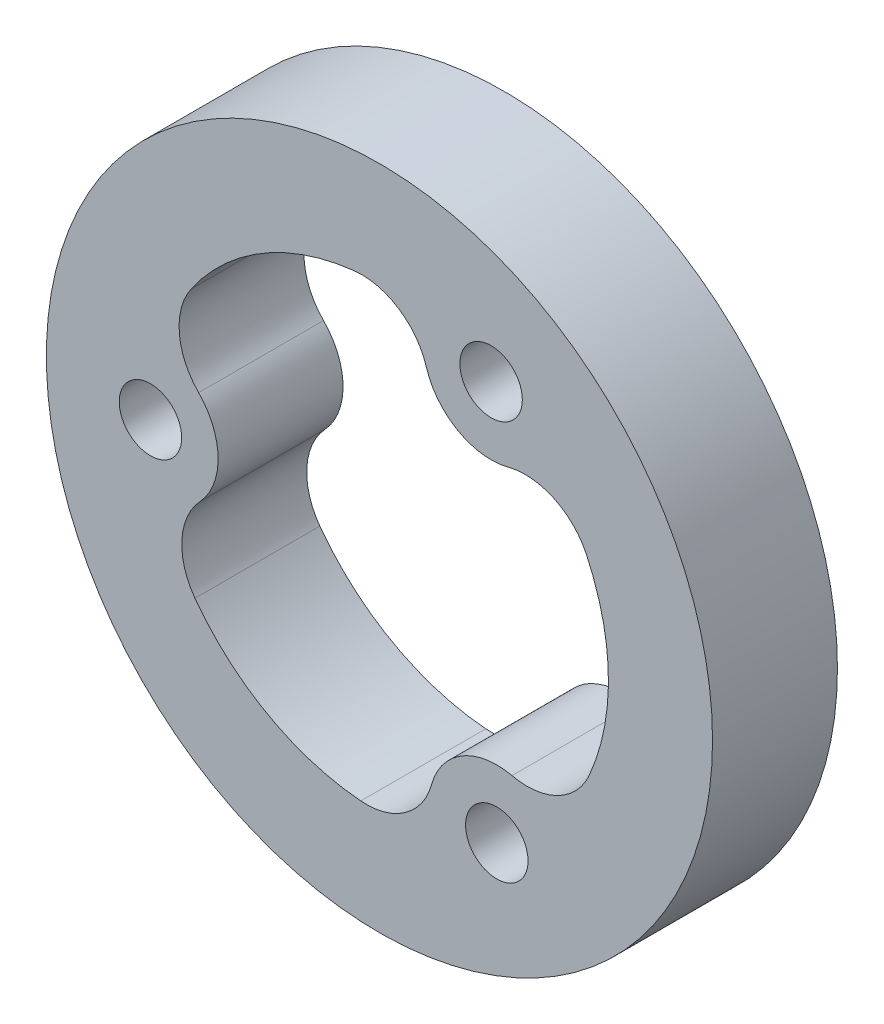
SolidWorks part; units mm, degrees
ref_plane "Plan de face" through (0, 0, 0) normal (0, 0, 1) x (1, 0, 0)
ref_plane "Plan de dessus" through (0, 0, 0) normal (0, 1, 0) x (1, 0, 0)
ref_plane "Plan de droite" through (0, 0, 0) normal (1, 0, 0) x (0, 0, -1)
sketch "Esquisse1" plane through (0, 0, 0) normal (0, 0, 1) x (1, 0, 0)
  line L0 (5.3623, 9.6045) -> (0, 0) construction
  circle A0 centre (0, 0) radius 16
  arc A2 (-8.6215, -2.3744) -> (-8.6863, 2.1252) centre (-10.9989, -0.1583) ccw
  circle A3 centre (-10.9989, -0.1583) radius 1.5
  arc A4 (-8.6215, -2.3744) -> (-8.8628, -6.5154) centre (-6.2442, -4.5904) ccw
  arc A5 (-9.0466, 6.2577) -> (-8.6863, 2.1252) centre (-6.3738, 4.4088) ccw
  arc A6 (-8.8628, -6.5154) -> (-0.896, -10.9635) centre (0, 0) ccw
  circle A7 centre (-10.9989, -0.1583) radius 3.25 construction
  circle A8 centre (5.3623, 9.6045) radius 3.25 construction
  circle A9 centre (5.3623, 9.6045) radius 1.5
  arc A10 (9.9426, 4.7058) -> (6.1837, 6.4599) centre (7.005, 3.3154) ccw
  arc A11 (2.2545, 8.6537) -> (6.1837, 6.4599) centre (5.3623, 9.6045) ccw
  arc A12 (2.2545, 8.6537) -> (-1.2111, 10.9331) centre (-0.8533, 7.7029) ccw
  circle A13 centre (5.6365, -9.4461) radius 3.25 construction
  circle A14 centre (5.6365, -9.4461) radius 1.5
  arc A15 (-0.896, -10.9635) -> (2.5026, -8.5852) centre (-0.6312, -7.7242) ccw
  arc A16 (6.367, -6.2793) -> (2.5026, -8.5852) centre (5.6365, -9.4461) ccw
  arc A17 (6.367, -6.2793) -> (10.0739, -4.4177) centre (7.0975, -3.1125) ccw
  arc A18 (10.0739, -4.4177) -> (9.9426, 4.7058) centre (0, 0) ccw
  circle A19 centre (0, 0) radius 7.75 construction
  arc A20 (-1.2111, 10.9331) -> (-9.0466, 6.2577) centre (0, 0) ccw
  point P32 (0, 0)
  dimension "D1" = 32
  dimension "D2" = 6.5
  dimension "D3" = 3
  dimension "D4" = 3
  dimension "D5" = 15.5
  dimension "D6" = 11
extrude "Boss.-Extru.1" add sketch "Esquisse1" along normal blind 6
